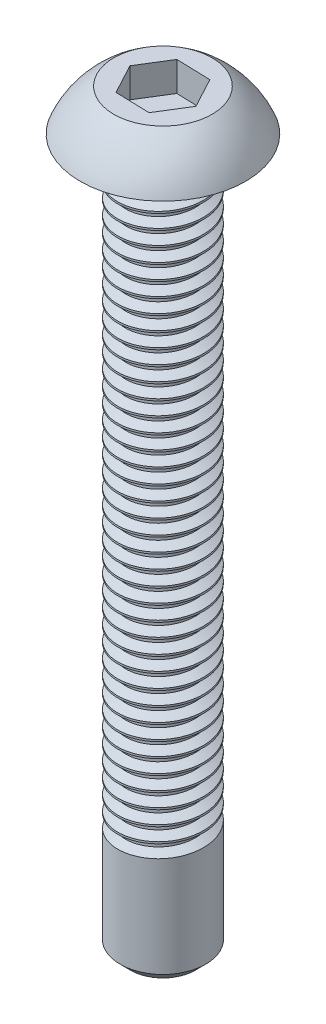
SolidWorks part; units mm, degrees
material "AISI 304"
ref_plane "Front Plane" through (0, 0, 0) normal (0, 0, 1) x (1, 0, 0)
ref_plane "Top Plane" through (0, 0, 0) normal (0, 1, 0) x (1, 0, 0)
ref_plane "Right Plane" through (0, 0, 0) normal (1, 0, 0) x (0, 0, -1)
sketch "Sketch1" plane through (0, 0, 0) normal (1, 0, 0) x (0, 0, -1)
  line L0 (0, 3.928) -> (0, 3.1683) construction
  line L1 (-2.8, 1.2683) -> (-1.45, 1.2683)
  line L2 (-1.45, 1.2683) -> (-1.45, -22.7317)
  line L3 (-1.6623, 2.6683) -> (0, 2.6683)
  line L4 (0, 2.6683) -> (0, -22.7317)
  line L5 (0, -22.7317) -> (-1.45, -22.7317)
  line L6 (0, 2.6683) -> (0, -3.4668) construction
  arc A0 (-2.8, 1.2683) -> (-1.6623, 2.6683) centre (0, 0.1552) cw
  point P10 (0, 3.1683)
  dimension "D1" = 2.9
  dimension "D2" = 5.6
  dimension "D3" = 1.9
  dimension "D4" = 24
  dimension "D5" = 1.4
revolve "Revolve1" add sketch "Sketch1" angle 360 about L0
sketch "Sketch2" plane through (0, 2.6683, 0) normal (0, 1, 0) x (1, 0, 0)
  line L1 (-0.5457, 1.0176) -> (-1.1541, 0.0363)
  line L2 (-1.1541, 0.0363) -> (-0.6085, -0.9814)
  line L3 (-0.6085, -0.9814) -> (0.5457, -1.0176)
  line L4 (0.5457, -1.0176) -> (1.1541, -0.0363)
  line L5 (1.1541, -0.0363) -> (0.6085, 0.9814)
  line L6 (0.6085, 0.9814) -> (-0.5457, 1.0176)
  circle A0 centre (0, 0) radius 1 construction
  dimension "D1" = 2
extrude "Cut-Extrude1" cut sketch "Sketch2" against normal blind 1
chamfer "Chamfer1" distance 0.35 angle 45 1 edges at (0, -22.7317, 1.45)
thread "Thread1" pitch 0.5 method cut profile "Thread Profile1" start angle 0, offset 0, length 20, pitch 0.5, diameter 2.9
ref_plane "Plane1" through (-1.45, 1.2683, 0) normal (0, 0, 1) x (-1, 0, 0)
sketch "Thread Profile1" plane through (-1.45, 1.2683, 0) normal (0, 0, 1) x (-1, 0, 0)
  line L0 (0, 0) -> (0, 0.5) construction
  line L11 (0, 0) -> (0, 0.4375)
  line L12 (0, 0.4375) -> (-0.2706, 0.2812)
  line L13 (-0.2706, 0.2812) -> (-0.2706, 0.1562)
  line L15 (-0.2706, 0.1562) -> (0, 0)
  line L17 (-0.2706, 0.2187) -> (0, 0.2187) construction
  point P2 (0, 0)
  dimension "Pitch" = 0.5
  dimension "Profile_Angle" = 60
  dimension "Profile_Land" = 0.125
  dimension "Profile_Height" = 0.2706
